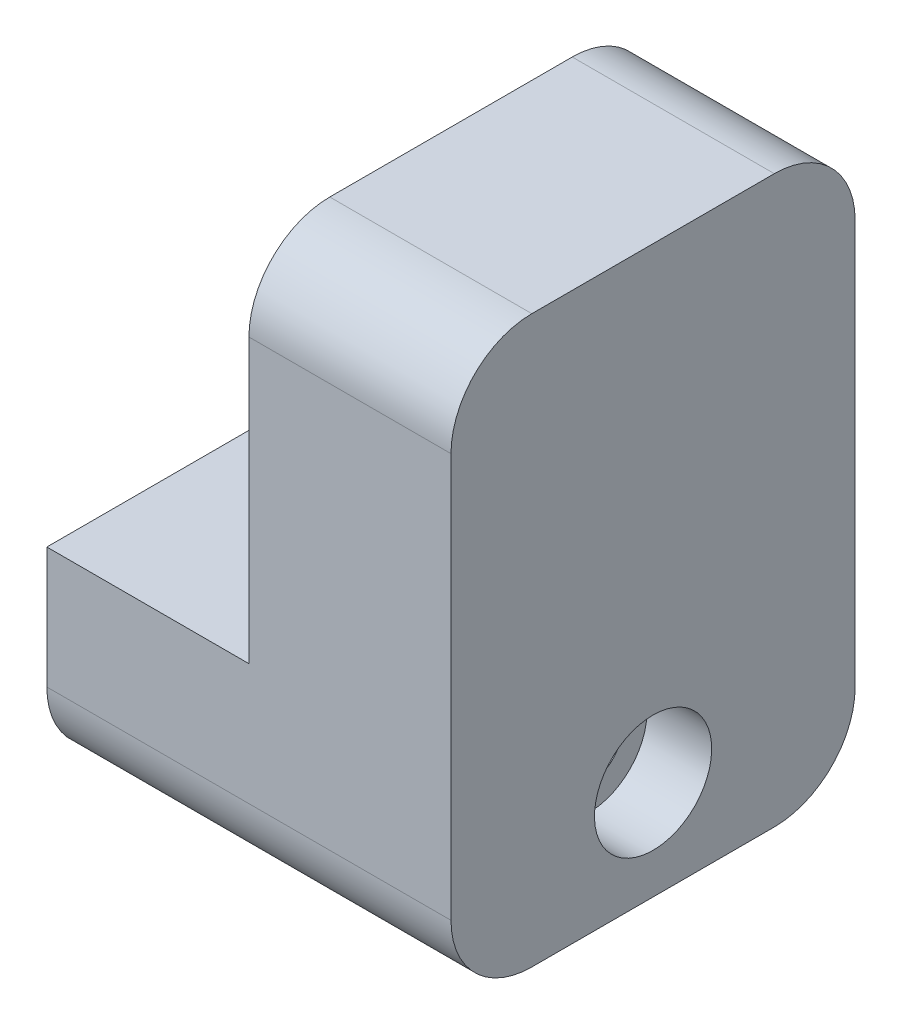
SolidWorks part; units mm, degrees
ref_plane "Front Plane" through (0, 0, 0) normal (0, 0, 1) x (1, 0, 0)
ref_plane "Top Plane" through (0, 0, 0) normal (0, 1, 0) x (1, 0, 0)
ref_plane "Right Plane" through (0, 0, 0) normal (1, 0, 0) x (0, 0, -1)
sketch "Profile" plane through (0, 0, 0) normal (0, 0, 1) x (1, 0, 0)
  line L1 (-6.35, 22.86) -> (6.35, 22.86)
  line L2 (-6.35, 22.86) -> (-6.35, 0)
  line L3 (-6.35, 0) -> (6.35, 0)
  line L4 (6.35, 22.86) -> (6.35, 0)
  line L5 (0, 0) -> (6.35, 0)
  line L6 (0, 0) -> (0, -12.7)
  line L7 (0, -12.7) -> (6.35, -12.7)
  line L8 (6.35, 0) -> (6.35, -12.7)
  dimension "D1" = 22.86
  dimension "D2" = 12.7
  dimension "D3" = 6.35
  dimension "D4" = 12.7
extrude "Boss-Extrude1" add sketch "Profile" along normal mid plane 25.4 contours L4 L1 L2 L3 | L8 L3 L6 L7 region at (0, 11.43, 0) region at (3.175, -6.35, 0)
sketch "Sketch7" plane through (0, 0, 12.7) normal (0, 0, 1) x (1, 0, 0)
  line L0 (0, -12.7) -> (6.35, -12.7) construction
  line L1 (0, 0) -> (-19.05, 0)
  line L2 (0, 0) -> (0, -12.7)
  line L3 (0, -12.7) -> (-19.05, -12.7)
  line L4 (-19.05, 0) -> (-19.05, -12.7)
  line L5 (-6.35, 22.86) -> (-6.35, 0) construction
  dimension "D1" = 12.7
extrude "Boss-Extrude2" add sketch "Sketch7" against normal up to surface (25.4 mm away) up to face at (0, 3.3867, -12.7)
sketch "ScrewHole" plane through (-19.05, 0, 0) normal (-1, 0, 0) x (0, 0, 1)
  line L0 (-12.7, 0) -> (12.7, 0) construction
  circle A0 centre (0, -6.477) radius 2.159
  dimension "D1" = 4.318
  dimension "D2" = 6.477
extrude "Cut-Extrude1" cut sketch "ScrewHole" against normal through all both and the other way through all
sketch "Sketch3" plane through (6.35, 0, 0) normal (1, 0, 0) x (0, 0, -1)
  circle A0 centre (0, -6.477) radius 2.159 construction
  circle A1 centre (0, -6.477) radius 2.159
  circle A2 centre (0, -6.477) radius 3.683
  dimension "D1" = 7.366
extrude "Cut-Extrude2" cut sketch "Sketch3" against normal blind 4.064
sketch "Sketch10" plane through (-6.35, 0, 0) normal (-1, 0, 0) x (0, 0, 1)
  line L0 (-12.7, 22.86) -> (-12.7, 0) construction
  line L1 (-10.16, 17.78) -> (10.16, 17.78) construction
  line L2 (-10.16, 17.78) -> (-10.16, 5.08) construction
  line L3 (-10.16, 5.08) -> (10.16, 5.08) construction
  line L4 (10.16, 17.78) -> (10.16, 5.08) construction
  circle A0 centre (-10.16, 17.78) radius 1.143
  circle A1 centre (10.16, 17.78) radius 1.143
  circle A2 centre (10.16, 5.08) radius 1.143
  circle A3 centre (-10.16, 5.08) radius 1.143
  point P8 (0, 5.08)
  point P12 (-12.7, 11.43)
  point P13 (-10.16, 11.43)
  dimension "D1" = 2.286
  dimension "D2" = 2.286
  dimension "D3" = 2.286
  dimension "D4" = 2.286
  dimension "D5" = 20.32
  dimension "D6" = 12.7
extrude "Cut-Extrude3" cut sketch "Sketch10" against normal blind 7.62
fillet "Fillet6" radius 5.08 4 edges at (-6.35, -12.7, 12.7) (-6.35, -12.7, -12.7) (0, 22.86, -12.7) (0, 22.86, 12.7)
